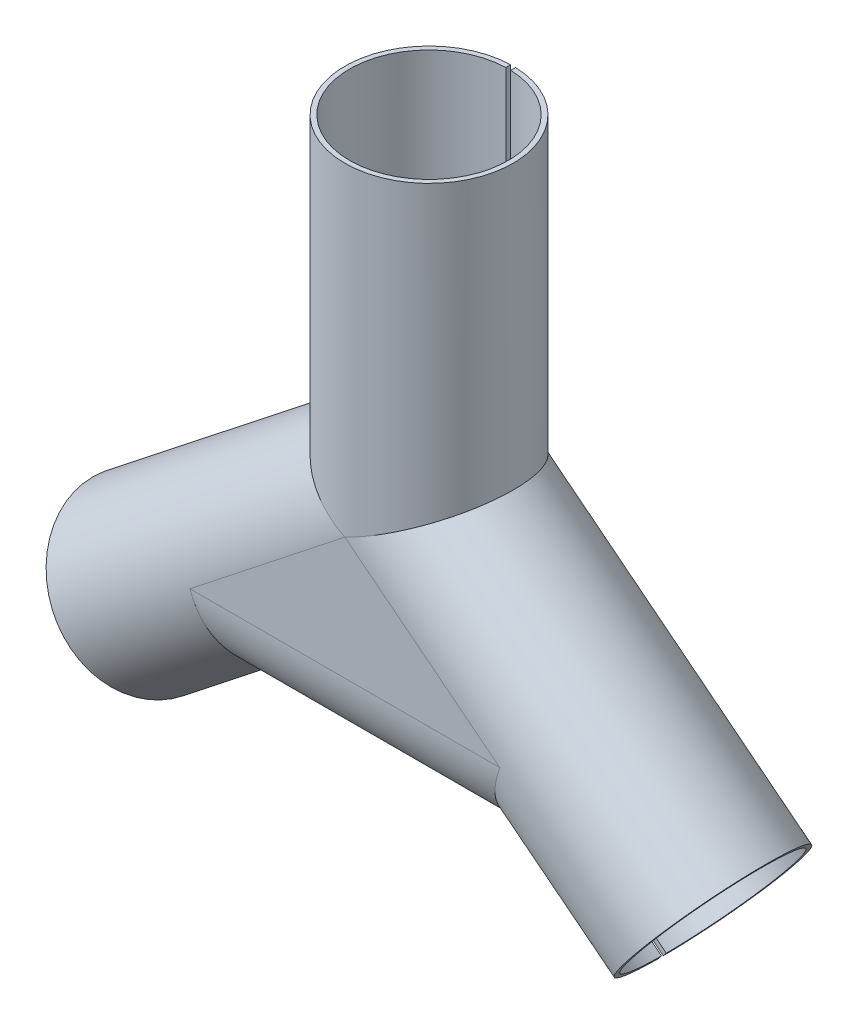
SolidWorks part; units mm, degrees
ref_plane "前视基准面" through (0, 0, 0) normal (0, 0, 1) x (1, 0, 0)
ref_plane "上视基准面" through (0, 0, 0) normal (0, 1, 0) x (1, 0, 0)
ref_plane "右视基准面" through (0, 0, 0) normal (1, 0, 0) x (0, 0, -1)
sketch "草图1" plane through (0, 0, 0) normal (0, 0, 1) x (1, 0, 0)
  line L0 (0, 67.2887) -> (0, 0) construction
  line L1 (0, 0) -> (-59.0019, -46.5051) construction
  line L2 (0, 0) -> (59.0019, -46.5051) construction
  line L3 (-17.4845, 67.2887) -> (17.4845, 67.2887) construction
  line L4 (69.8252, -32.7733) -> (48.1786, -60.2368) construction
  line L5 (48.1786, -60.2368) -> (26.138, -42.8645) construction
  line L6 (26.138, -42.8645) -> (-26.138, -42.8645) construction
  line L7 (-26.138, -42.8645) -> (-48.1786, -60.2368) construction
  line L8 (-48.1786, -60.2368) -> (-69.8252, -32.7733) construction
  line L9 (-69.8252, -32.7733) -> (-17.4845, 8.4815) construction
  line L10 (-17.4845, 8.4815) -> (-17.4845, 67.2887) construction
  line L11 (17.4845, 67.2887) -> (17.4845, 8.4815) construction
  line L12 (17.4845, 8.4815) -> (69.8252, -32.7733) construction
  line L13 (0, 0) -> (0, -42.8645) construction
  line L14 (-17.4845, 8.4815) -> (0, 0) construction
  line L15 (0, 0) -> (17.4845, 8.4815) construction
  line L16 (-26.138, -42.8645) -> (-32.2002, -25.3801) construction
  line L17 (26.138, -42.8645) -> (32.2002, -25.3801) construction
  line L18 (-32.2002, -25.3801) -> (32.2002, -25.3801) construction
  line L19 (26.138, -42.8645) -> (26.138, -25.3801) construction
  line L20 (0, 67.2887) -> (17.4845, 67.2887) construction
  line L21 (0, -42.8645) -> (0, -43.8645) construction
  line L22 (0, 0) -> (0, 67.2887)
  dimension "R" = 17.4845
  dimension "L1" = 67.2887
  dimension "L3" = 75.1262
  dimension "L2" = 41
  dimension "B" = 103.51
  dimension "t" = 1
sketch "草图2" plane through (0, 0, 0) normal (0, 1, 0) x (1, 0, 0)
  line L0 (0, 17.4845) -> (0, -17.4845) construction
  circle A0 centre (0, 0) radius 17.4845
extrude "拉伸-薄壁1" add sketch "草图2" along normal up to vertex (67.2887 mm away) thin up to point (0, 67.2887, 0) thin type one direction reverse wall 1
ref_plane "基准面1" through (59.0019, -46.5051, 0) normal (0.7854, -0.619, 0) x (0, 0, -1)
sketch "草图3" plane through (59.0019, -46.5051, 0) normal (0.7854, -0.619, 0) x (0, 0, -1)
  line L0 (0, 17.4845) -> (0, -17.4845) construction
  circle A0 centre (0, 0) radius 17.4845
extrude "拉伸-薄壁2" add sketch "草图3" against normal up to vertex (75.1262 mm away) separate body thin up to point (0, 0, 0) thin type one direction reverse wall 1
ref_plane "基准面2" through (26.138, -25.3801, 0) normal (1, 0, 0) x (0, 0, -1)
sketch "草图4" plane through (26.138, -25.3801, 0) normal (1, 0, 0) x (0, 0, -1)
  circle A0 centre (0, 0) radius 17.4845
extrude "拉伸-薄壁3" add sketch "草图4" against normal up to vertex (58.3382 mm away) and the other way up to vertex (6.0622 mm away) separate body thin up to point (-32.2002, -25.3801, 0) other way up to point (32.2002, -25.3801, 0) thin type one direction reverse wall 1
ref_plane "基准面3" through (0, 0, 17.4845) normal (0, 0, 1) x (1, 0, 0)
sketch "草图6" plane through (0, 0, 0) normal (0, 0, 1) x (1, 0, 0)
  line L0 (0, 0) -> (17.4845, 8.4815) construction
  line L1 (-17.4845, 8.4815) -> (0, 0) construction
  line L2 (-17.4845, 8.4815) -> (-17.4845, 67.2887) construction
  line L3 (17.4845, 67.2887) -> (17.4845, 8.4815) construction
  line L4 (-17.4845, 67.2887) -> (17.4845, 67.2887) construction
  line L5 (0, 0) -> (17.4845, 8.4815)
  line L6 (-17.4845, 8.4815) -> (0, 0)
  line L7 (-17.4845, 8.4815) -> (-17.4845, 67.2887)
  line L8 (17.4845, 67.2887) -> (17.4845, 8.4815)
  line L9 (-17.4845, 67.2887) -> (17.4845, 67.2887)
extrude "切除-拉伸1" cut sketch "草图6" against normal through all and the other way through all flip side to cut
sketch "草图7" plane through (0, 0, 0) normal (0, 0, 1) x (1, 0, 0)
  line L0 (0, 0) -> (17.4845, 8.4815) construction
  line L1 (17.4845, 8.4815) -> (69.8252, -32.7733) construction
  line L2 (69.8252, -32.7733) -> (48.1786, -60.2368) construction
  line L3 (48.1786, -60.2368) -> (26.138, -42.8645) construction
  line L4 (26.138, -42.8645) -> (32.2002, -25.3801) construction
  line L5 (0, 0) -> (17.4845, 8.4815)
  line L6 (17.4845, 8.4815) -> (69.8252, -32.7733)
  line L7 (69.8252, -32.7733) -> (48.1786, -60.2368)
  line L8 (48.1786, -60.2368) -> (26.138, -42.8645)
  line L9 (26.138, -42.8645) -> (32.2002, -25.3801)
  line L10 (32.2002, -25.3801) -> (0, 0)
extrude "切除-拉伸2" cut sketch "草图7" against normal through all and the other way through all flip side to cut
sketch "草图8" plane through (0, 0, 0) normal (0, 0, 1) x (1, 0, 0)
  line L0 (26.138, -42.8645) -> (32.2002, -25.3801) construction
  line L1 (-32.2002, -25.3801) -> (32.2002, -25.3801) construction
  line L2 (26.138, -42.8645) -> (-26.138, -42.8645) construction
  line L3 (-26.138, -42.8645) -> (-32.2002, -25.3801) construction
  line L4 (26.138, -42.8645) -> (32.2002, -25.3801)
  line L5 (-32.2002, -25.3801) -> (32.2002, -25.3801)
  line L6 (26.138, -42.8645) -> (-26.138, -42.8645)
  line L7 (-26.138, -42.8645) -> (-32.2002, -25.3801)
extrude "切除-拉伸3" cut sketch "草图8" against normal through all and the other way through all flip side to cut
sketch "草图5" plane through (0, 0, 17.4845) normal (0, 0, 1) x (1, 0, 0)
  line L0 (0, 0) -> (-32.2002, -25.3801)
  line L1 (-32.2002, -25.3801) -> (32.2002, -25.3801)
  line L2 (32.2002, -25.3801) -> (0, 0)
extrude "凸台-拉伸1" add sketch "草图5" against normal blind 1
sketch "草图9" plane through (59.0019, -46.5051, 0) normal (0.7854, -0.619, 0) x (0, 0, -1)
  line L0 (0, 0) -> (0, -17.4845)
extrude "切除-拉伸-薄壁1" cut sketch "草图9" against normal through all thin thin type mid plane wall 1
extrude "切除-拉伸-薄壁2" cut sketch "草图1" against normal through all thin thin type mid plane wall 1
mirror "镜向1" about plane through (0, 0, 0) normal (0, 0, 1) of "凸台-拉伸1"
mirror "镜向2" about plane through (0, 0, 0) normal (1, 0, 0) of bodies 110 106
equation "\"D5@拉伸-薄壁1\" = \"t@草图1\""
equation "\"D5@拉伸-薄壁3\" = \"t@草图1\""
equation "\"D5@拉伸-薄壁2\" = \"t@草图1\""
equation "\"D1@凸台-拉伸1\" = \"t@草图1\""
